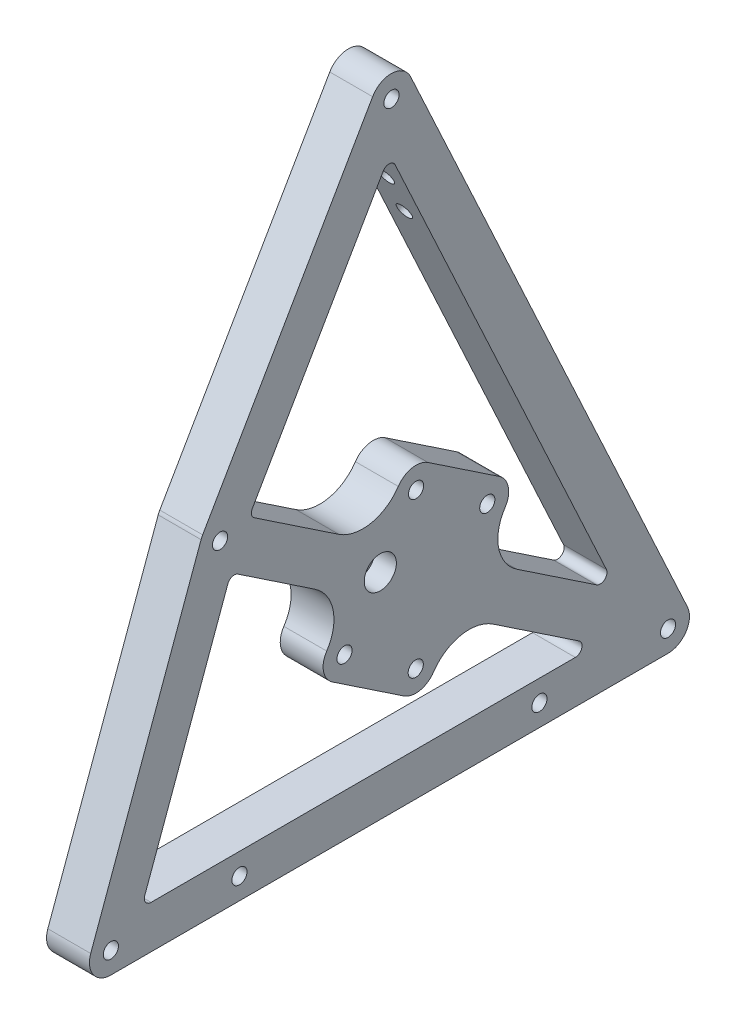
SolidWorks part; units mm, degrees
ref_plane "Front Plane" through (0, 0, 0) normal (0, 0, 1) x (1, 0, 0)
ref_plane "Top Plane" through (0, 0, 0) normal (0, 1, 0) x (1, 0, 0)
ref_plane "Right Plane" through (0, 0, 0) normal (1, 0, 0) x (0, 0, -1)
sketch "Sketch1" plane through (0, 0, 0) normal (1, 0, 0) x (0, 0, -1)
  line L0 (0, 0) -> (50.8, 87.9882) construction
  line L1 (0, 0) -> (-32.357, -88.9) construction
  line L2 (-32.357, -88.9) -> (132.743, -88.9) construction
  line L3 (132.743, -88.9) -> (0, 0) construction
  line L4 (0, 0) -> (117.1773, 0) construction
  line L5 (50.8, 87.9882) -> (132.743, -88.9) construction
  circle A0 centre (0, 0) radius 50.8 construction
  circle A1 centre (28.575, 49.4934) radius 6.35 construction
  circle A2 centre (47.4848, -31.8013) radius 6.35 construction
  dimension "D4" = 101.6
  dimension "D5" = 12.7
  dimension "D8" = 12.7
  dimension "D1" = 60
  dimension "D2" = 70
  dimension "D3" = 165.1
  dimension "D6" = 101.6
  dimension "D7" = 88.9
sketch "Sketch2" plane through (0, 0, 0) normal (1, 0, 0) x (0, 0, -1)
  line L0 (-23.2882, -82.55) -> (3.1967, -9.7834)
  line L1 (3.1967, -9.7834) -> (111.8498, -82.55)
  line L2 (111.8498, -82.55) -> (-23.2882, -82.55)
  line L3 (8.6152, 1.8728) -> (117.4643, -71.0251)
  line L4 (117.4643, -71.0251) -> (50.2711, 74.0229)
  line L5 (50.2711, 74.0229) -> (8.6152, 1.8728)
  line L6 (-41.4257, -95.25) -> (142.6829, -95.25)
  line L7 (142.6829, -95.25) -> (51.3289, 101.9534)
  line L8 (51.3289, 101.9534) -> (-5.4332, 3.6387)
  line L9 (-5.4332, 3.6387) -> (-41.4257, -95.25)
  line L10 (0, 0) -> (-32.357, -88.9) construction
  line L11 (0, 0) -> (50.8, 87.9882) construction
  line L12 (50.8, 87.9882) -> (132.743, -88.9) construction
  line L13 (132.743, -88.9) -> (0, 0) construction
  line L14 (-32.357, -88.9) -> (132.743, -88.9) construction
  line L15 (50.8, 87.9882) -> (132.743, -88.9) construction
  line L16 (132.743, -88.9) -> (0, 0) construction
  line L17 (-32.357, -88.9) -> (132.743, -88.9) construction
  line L18 (0, 0) -> (-32.357, -88.9) construction
  line L19 (0, 0) -> (50.8, 87.9882) construction
  circle A0 centre (0, 0) radius 2.25
  circle A1 centre (50.8, 87.9882) radius 2.25
  circle A2 centre (-32.357, -88.9) radius 2.25
  circle A3 centre (132.743, -88.9) radius 2.25
  circle A4 centre (5.743, -88.9) radius 2.25
  circle A5 centre (94.643, -88.9) radius 2.25
  dimension "D5" = 4.5
  dimension "D6" = 4.5
  dimension "D7" = 4.5
  dimension "D8" = 4.5
  dimension "D1" = 12.7
  dimension "D2" = 12.7
  dimension "D3" = 12.7
  dimension "D4" = 12.7
  dimension "D9" = 38.1
  dimension "D10" = 38.1
extrude "Boss-Extrude1" add sketch "Sketch2" along normal blind 12.7
fillet "Fillet1" radius 6.35 4 edges at (6.35, -95.25, 41.4257) (6.35, -95.25, -142.6829) (6.35, 101.9534, -51.3289) (6.35, 3.6387, 5.4332)
fillet "Fillet2" radius 2 6 edges at (6.35, 74.0229, -50.2711) (6.35, 1.8728, -8.6152) (6.35, -71.0251, -117.4643) (6.35, -82.55, -111.8498) (6.35, -82.55, 23.2882) (6.35, -9.7834, -3.1967)
sketch "Sketch3" plane through (0, 0, 0) normal (1, 0, 0) x (0, 0, -1)
  line L0 (106.3822, -78.8882) -> (5.3164, -11.203) construction
  line L1 (10.1699, 0.8315) -> (111.5391, -67.0569) construction
  line L2 (106.3822, -78.8882) -> (5.3164, -11.203)
  line L3 (10.1699, 0.8315) -> (111.5391, -67.0569)
  line L4 (45.7422, -22.9917) -> (77.3987, -44.1925)
  line L5 (45.7422, -22.9917) -> (56.3426, -7.1634)
  line L6 (77.3987, -44.1925) -> (87.9991, -28.3643)
  line L7 (56.3426, -7.1634) -> (87.9991, -28.3643)
  line L8 (38.6752, -33.5439) -> (70.3317, -54.7447)
  line L9 (38.6752, -33.5439) -> (28.0748, -49.3721)
  line L10 (70.3317, -54.7447) -> (59.7313, -70.573)
  line L11 (28.0748, -49.3721) -> (59.7313, -70.573)
  line L12 (36.8843, -47.6295) -> (57.9887, -61.7634) construction
  line L13 (36.8843, -47.6295) -> (58.0852, -15.973) construction
  line L14 (57.9887, -61.7634) -> (79.1895, -30.1069) construction
  line L15 (58.0852, -15.973) -> (79.1895, -30.1069) construction
  circle A0 centre (47.4848, -31.8013) radius 4.7625
  circle A1 centre (36.8843, -47.6295) radius 2.25
  circle A2 centre (57.9887, -61.7634) radius 2.25
  circle A3 centre (79.1895, -30.1069) radius 2.25
  circle A4 centre (58.0852, -15.973) radius 2.25
  circle A5 centre (47.4848, -31.8013) radius 2.25
  dimension "D1" = 9.525
  dimension "D5" = 4.5
  dimension "D10" = 4.5
  dimension "D2" = 6.35
  dimension "D3" = 38.1
  dimension "D4" = 19.05
  dimension "D6" = 6.35
  dimension "D7" = 6.35
  dimension "D8" = 25.4
  dimension "D9" = 38.1
extrude "Cut-Extrude2" cut sketch "Sketch3" against normal blind 6.35 from surface contours A0 region at (0, -31.8013, -42.857) starting at face at (12.7, -88.9, -7.993)
extrude "Boss-Extrude2" add sketch "Sketch3<3>" along normal blind 12.7 contours L7 L5 L3 L6 A4 A3 | L9 L11 L10 L2 A2 A1 region at (0, -51.9375, -49.2842) region at (0, -25.7989, -66.7896)
sketch "Sketch3<3>" plane through (0, 0, 0) normal (1, 0, 0) x (0, 0, -1) same geometry as "Sketch3"
fillet "Fillet3" radius 6.35 4 edges at (6.35, -49.3721, -28.0748) (6.35, -70.573, -59.7313) (6.35, -28.3643, -87.9991) (6.35, -7.1634, -56.3426)
sketch "Sketch4" plane through (0, 37.5902, -81.145) normal (0, 0.4203, -0.9074) x (-1, 0, 0)
  line L0 (0, 58.6981) -> (-12.7, 58.6981) construction
  line L1 (0, -136.4618) -> (0, 58.6981) construction
  circle A0 centre (-6.35, 20.5981) radius 2.25
  circle A1 centre (-6.35, 33.2981) radius 2.25
  point P4 (0, 0)
  dimension "D4" = 4.5
  dimension "D5" = 4.5
  dimension "D1" = 25.4
  dimension "D2" = 12.7
  dimension "D3" = 6.35
extrude "Cut-Extrude3" cut sketch "Sketch4" against normal up to next
extrude "Cut-Extrude4" cut sketch "Sketch3<4>" against normal through all from surface contours A5 region at (0, -31.8013, -47.4848) starting at face at (12.7, -31.8013, -49.7348)
sketch "Sketch3<4>" plane through (0, 0, 0) normal (1, 0, 0) x (0, 0, -1) same geometry as "Sketch3"
fillet "Fillet4" radius 12.7 4 edges at (6.35, -44.1925, -77.3987) (6.35, -54.7447, -70.3317) (6.35, -22.9917, -45.7422) (6.35, -33.5439, -38.6752)
